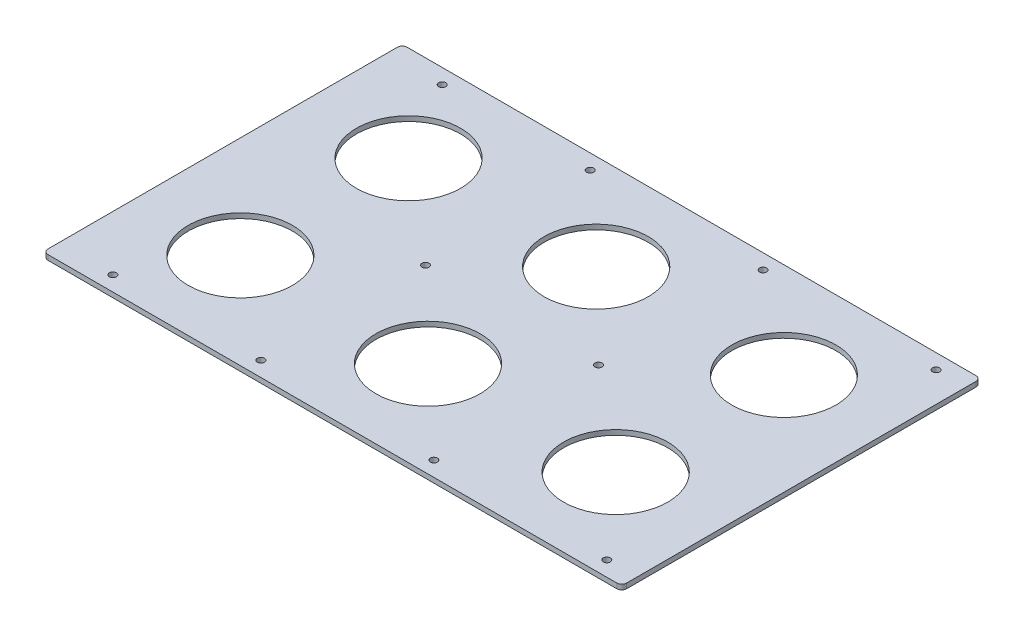
SolidWorks part; units mm, degrees
material "ABS"
ref_plane "Front" through (0, 0, 0) normal (0, 0, 1) x (1, 0, 0)
ref_plane "Top" through (0, 0, 0) normal (0, 1, 0) x (1, 0, 0)
ref_plane "Right" through (0, 0, 0) normal (1, 0, 0) x (0, 0, -1)
sketch "Sketch1" plane through (0, 0, 0) normal (0, 1, 0) x (1, 0, 0)
  line L1 (-180.975, 114.3) -> (180.975, 114.3)
  line L2 (-184.15, 111.125) -> (-184.15, -111.125)
  line L3 (-180.975, -114.3) -> (180.975, -114.3)
  line L4 (184.15, 111.125) -> (184.15, -111.125)
  line L5 (-184.15, 114.3) -> (184.15, -114.3) construction
  line L6 (-184.15, -114.3) -> (184.15, 114.3) construction
  circle A0 centre (119.5086, -53.5178) radius 33.147
  arc A1 (-184.15, -111.125) -> (-180.975, -114.3) centre (-180.975, -111.125) ccw
  arc A2 (180.975, -114.3) -> (184.15, -111.125) centre (180.975, -111.125) ccw
  arc A3 (184.15, 111.125) -> (180.975, 114.3) centre (180.975, 111.125) ccw
  arc A4 (-180.975, 114.3) -> (-184.15, 111.125) centre (-180.975, 111.125) ccw
  circle A21 centre (-55.0333, 0) radius 2.2479 construction
  circle A22 centre (55.0333, 0) radius 2.2479 construction
  circle A23 centre (-55.0333, 0) radius 2.2479
  circle A24 centre (55.0333, 0) radius 2.2479
  circle A25 centre (119.5086, 53.5178) radius 33.147
  circle A26 centre (0.0643, 53.5178) radius 33.147
  circle A27 centre (0.0643, -53.5178) radius 33.147
  circle A28 centre (-119.38, 53.5178) radius 33.147
  circle A29 centre (-119.38, -53.5178) radius 33.147
  arc A34 (-143.7521, 103.8733) -> (-143.7521, 3.1623) centre (-119.38, 53.5178) ccw construction
  arc A35 (-24.3078, 103.8733) -> (-24.3078, 3.1623) centre (0.0643, 53.5178) ccw construction
  arc A36 (95.1365, 103.8733) -> (95.1365, 3.1623) centre (119.5086, 53.5178) ccw construction
  arc A37 (-143.7521, -3.1623) -> (-143.7521, -103.8733) centre (-119.38, -53.5178) ccw construction
  arc A38 (-24.3078, -3.1623) -> (-24.3078, -103.8733) centre (0.0643, -53.5178) ccw construction
  arc A39 (95.1365, -3.1623) -> (95.1365, -103.8733) centre (119.5086, -53.5178) ccw construction
  circle A40 centre (-149.225, -104.775) radius 2.2479 construction
  circle A41 centre (-55.0333, -104.775) radius 2.2479 construction
  circle A42 centre (55.0333, -104.775) radius 2.2479 construction
  circle A43 centre (165.1, -104.775) radius 2.2479 construction
  circle A44 centre (-149.225, 104.775) radius 2.2479 construction
  circle A45 centre (-55.0333, 104.775) radius 2.2479 construction
  circle A46 centre (55.0333, 104.775) radius 2.2479 construction
  circle A47 centre (165.1, 104.775) radius 2.2479 construction
  circle A48 centre (-149.225, -104.775) radius 2.2479
  circle A49 centre (-55.0333, -104.775) radius 2.2479
  circle A50 centre (55.0333, -104.775) radius 2.2479
  circle A51 centre (165.1, -104.775) radius 2.2479
  circle A52 centre (-149.225, 104.775) radius 2.2479
  circle A53 centre (-55.0333, 104.775) radius 2.2479
  circle A54 centre (55.0333, 104.775) radius 2.2479
  circle A55 centre (165.1, 104.775) radius 2.2479
  point P0 (0, 0)
  dimension "D3" = 66.294
  dimension "D4" = 3.175
  dimension "D1" = 368.3
  dimension "D2" = 228.6
extrude "Boss-Extrude1" add sketch "Sketch1" along normal blind 3.175
